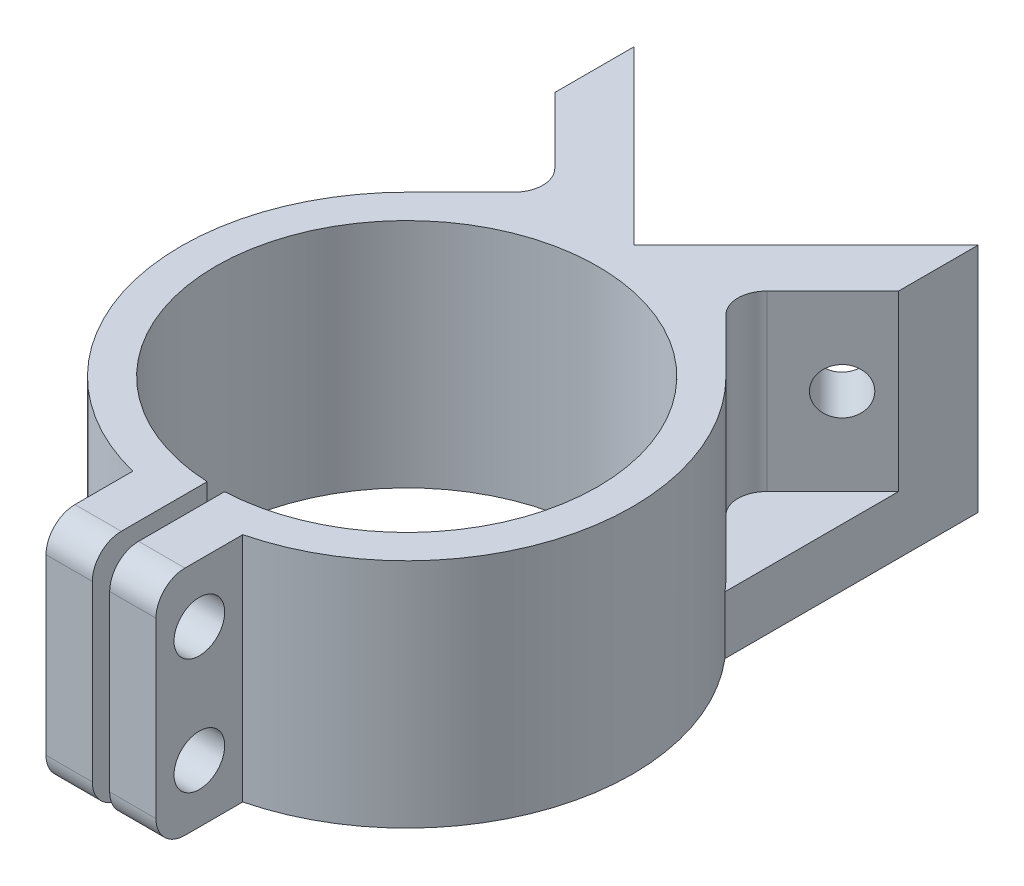
SolidWorks part; units mm, degrees
ref_plane "Front Plane" through (0, 0, 0) normal (0, 0, 1) x (1, 0, 0)
ref_plane "Top Plane" through (0, 0, 0) normal (0, 1, 0) x (1, 0, 0)
ref_plane "Right Plane" through (0, 0, 0) normal (1, 0, 0) x (0, 0, -1)
sketch "Sketch15" plane through (0, 0, 0) normal (0, 1, 0) x (0, 0, -1)
  line L24 (-32.9659, -1.5) -> (-52.8159, -1.5)
  line L25 (-52.8159, -9.5) -> (-37.8253, -9.5)
  line L26 (27.5772, -27.5772) -> (40.3682, -14.7861)
  line L27 (40.3682, -14.7861) -> (55.2821, -29.7)
  line L28 (55.2821, -29.7) -> (69, -29.7)
  line L29 (69, -29.7) -> (39.3, 0)
  line L30 (33, 0) -> (39.3, 0)
  line L39 (55.2821, -29.7) -> (40.3682, -14.7861)
  line L40 (40.3682, -14.7861) -> (27.5772, -27.5772)
  line L41 (25.2767, -29.7) -> (55.2821, -29.7)
  line L47 (-52.8159, -1.5) -> (-52.8159, -9.5)
  arc A9 (-37.8253, -9.5) -> (27.5772, -27.5772) centre (0, 0) ccw
  circle A11 centre (0, 0) radius 33 construction
  arc A12 (33, 0) -> (-32.9659, -1.5) centre (0, 0) cw
  circle A13 centre (0, 0) radius 39 construction
  arc A17 (25.2767, -29.7) -> (27.5772, -27.5772) centre (0, 0) ccw
  dimension "D4" = 66
  dimension "D8" = 78
  dimension "D1" = 6.3
  dimension "D2" = 1.5
  dimension "D3" = 29.7
  dimension "D5" = 29.7
  dimension "D6" = 19.85
  dimension "D7" = 8
  dimension "D9" = 9.7
extrude "Boss-Extrude7" add sketch "Sketch15" along normal blind 40 contours L30 A12 L24 L47 L25 A9 L26 L27 L28 L29 region at (34.2702, 0, -0.7793)
extrude "Boss-Extrude8" add sketch "Sketch15<4>" along normal blind 10 contours A9 L41 L27 L26 region at (24.7312, 0, -40.3602)
sketch "Sketch15<4>" plane through (0, 0, 0) normal (0, 1, 0) x (0, 0, -1) same geometry as "Sketch15"
sketch "Sketch16" plane through (-12.7911, 0, -12.7911) normal (0.7071, 0, 0.7071) x (-0.7071, 0, 0.7071)
  line L0 (-60.0914, -25) -> (-53.1893, -25) construction
  line L1 (-60.0914, -40) -> (-60.0914, -10) construction
  line L3 (-27.7893, -40) -> (-27.7893, 0) construction
  circle A0 centre (-53.1893, -25) radius 4
  dimension "D1" = 8
  dimension "D2" = 25.4
extrude "Cut-Extrude6" cut sketch "Sketch16" against normal through all
sketch "Sketch17" plane through (0, 0, 0) normal (1, 0, 0) x (0, -1, 0)
  line L0 (-20, -52.8159) -> (-20, -37.8253) construction
  line L1 (-40, -52.8159) -> (0, -52.8159) construction
  line L2 (-40, -37.8253) -> (0, -37.8253) construction
  line L3 (0, -45.3206) -> (-20, -45.3206) construction
  line L4 (0, -52.8159) -> (0, -37.8253) construction
  line L5 (-20, -45.3206) -> (-40, -45.3206) construction
  line L6 (-40, -52.8159) -> (-40, -37.8253) construction
  circle A0 centre (-30, -45.3206) radius 4.375
  circle A1 centre (-10, -45.3206) radius 4.375
  point P15 (-30, -45.3206)
  point P19 (-10, -45.3206)
  dimension "D1" = 8.75
extrude "Cut-Extrude7" cut sketch "Sketch17" along normal blind 10
fillet "Fillet2" radius 5 3 edges at (14.7861, 25, -40.3682) (5.5, 0, 52.8159) (5.5, 40, 52.8159)
mirror "Mirror2" about plane through (0, 40, 0) normal (-1, 0, 0) of bodies 128 125
